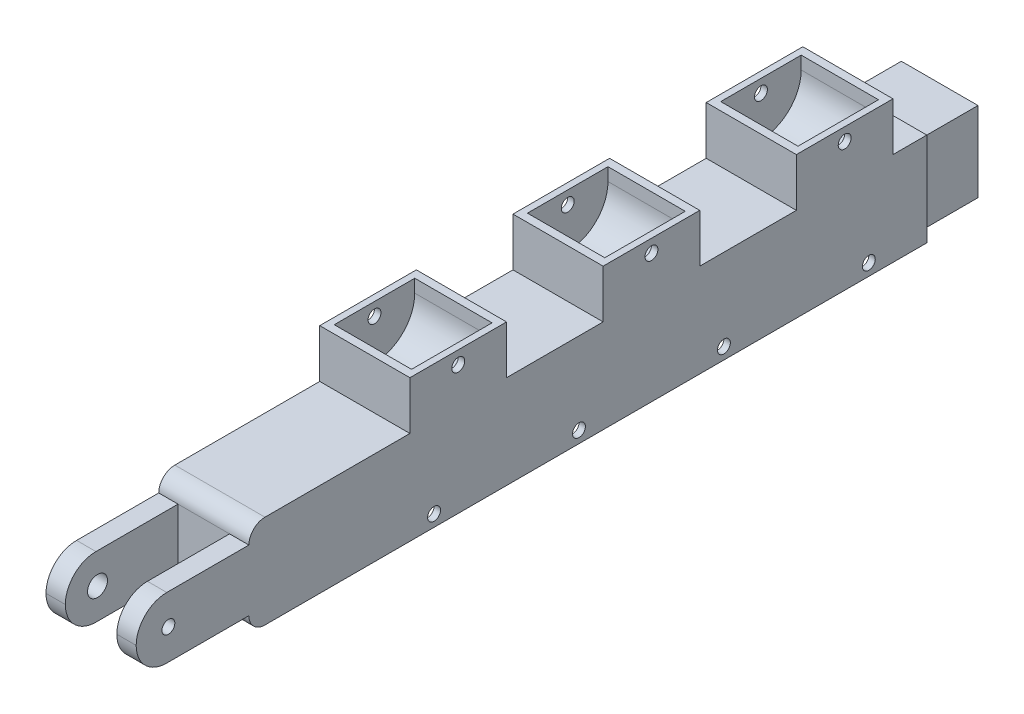
SolidWorks part; units mm, degrees
ref_plane "前视基准面" through (0, 0, 0) normal (0, 0, 1) x (1, 0, 0)
ref_plane "上视基准面" through (0, 0, 0) normal (0, 1, 0) x (1, 0, 0)
ref_plane "右视基准面" through (0, 0, 0) normal (1, 0, 0) x (0, 0, -1)
other "Configuration Table"
sketch "草图1" plane through (0, 0, 0) normal (1, 0, 0) x (0, 0, -1)
  line L0 (-150, 0) -> (150, 0) construction
  line L1 (-125, 14.5) -> (125, 14.5)
  line L2 (-125, 14.5) -> (-125, -14.5)
  line L3 (-125, -14.5) -> (125, -14.5)
  line L4 (125, 14.5) -> (125, -14.5)
  line L5 (-72.5, 29.5) -> (-72.5, 25.5)
  line L6 (-75, 14.5) -> (-45, 14.5)
  line L7 (-75, 14.5) -> (-75, 29.5)
  line L8 (-120, 10.8586) -> (120, 10.8586)
  line L9 (-120, 10.8586) -> (-120, -10.8586)
  line L10 (-120, -10.8586) -> (120, -10.8586)
  line L11 (120, 10.8586) -> (120, -10.8586)
  line L12 (-120, 10.8586) -> (120, -10.8586) construction
  line L13 (-120, -10.8586) -> (120, 10.8586) construction
  line L14 (-75, 29.5) -> (-45, 29.5)
  line L15 (-45, 14.5) -> (-45, 29.5)
  line L16 (-15, 14.5) -> (15, 14.5)
  line L17 (-15, 14.5) -> (-15, 29.5)
  line L18 (-15, 29.5) -> (15, 29.5)
  line L19 (15, 14.5) -> (15, 29.5)
  line L20 (45, 14.5) -> (75, 14.5)
  line L21 (45, 14.5) -> (45, 29.5)
  line L22 (45, 29.5) -> (75, 29.5)
  line L23 (75, 14.5) -> (75, 29.5)
  line L24 (-47.5, 29.5) -> (-47.5, 25.5)
  line L25 (-12.5, 29.5) -> (-12.5, 25.5)
  line L26 (12.5, 29.5) -> (12.5, 25.5)
  line L27 (47.5, 29.5) -> (47.5, 25.5)
  line L29 (72.5, 25.5) -> (72.5, 29.5)
  circle A2 centre (-67.5, -10.8586) radius 2
  circle A3 centre (-22.5, -10.8586) radius 2
  circle A4 centre (22.5, -10.8586) radius 2
  circle A5 centre (-60, 25.5) radius 2
  circle A6 centre (67.5, -10.8586) radius 2
  circle A7 centre (0, 25.5) radius 2
  circle A8 centre (60, 25.5) radius 2
  circle A9 centre (-60, 25.5) radius 12.5
  circle A10 centre (0, 25.5) radius 12.5
  circle A11 centre (60, 25.5) radius 12.5
  circle A12 centre (-67.5, -10.8586) radius 12.5
  circle A13 centre (-22.5, -10.8586) radius 12.5
  circle A14 centre (22.5, -10.8586) radius 12.5
  circle A15 centre (67.5, -10.8586) radius 12.5
  circle A16 centre (150, 0) radius 2
  circle A17 centre (-150, 0) radius 2
  circle A18 centre (-150, 0) radius 3.1
  point P10 (0, 0)
  point P12 (-125, 0)
  point P56 (-60, 29.5)
  point P62 (0, 29.5)
  point P64 (60, 29.5)
  dimension "D2" = 5
  dimension "D4" = 25
  dimension "D8" = 4
  dimension "D18" = 4
  dimension "D22" = 6.2
  dimension "D1" = 300
  dimension "D3" = 5
  dimension "D5" = 14.5
  dimension "D6" = 120
  dimension "D7" = 10.8586
  dimension "D9" = 52.5
  dimension "D10" = 45
  dimension "D11" = 45
  dimension "D12" = 45
  dimension "D13" = 60
  dimension "D14" = 60
  dimension "D15" = 60
  dimension "D16" = 60
  dimension "D17" = 52.5
  dimension "D19" = 30
  dimension "D20" = 4
  dimension "D21" = 15
extrude "凸台-拉伸1" add sketch "草图1" along normal blind 28 contours L1 L4 L3 L2 | L14 L15 L6 L7 | L18 L19 L16 L17 | L22 L23 L20 L21
extrude "切除-拉伸1" cut sketch "草图1<3>" along normal through all contours A2 | A3 | A4 | A6 | A8 | A7 | A5
sketch "草图1<3>" plane through (0, 0, 0) normal (1, 0, 0) x (0, 0, -1) same geometry as "草图1"
extrude "切除-拉伸2" cut sketch "草图1<5>" along normal offset from surface (24 mm away) 2 from offset 2 contours A9 L14 L5 | A9 L24 L14 | A10 L18 L25 | A10 L26 L18 | A11 L22 L27 | A11 L29 L22 | A12 | A9 | A13 | A10 | A14 | A11 | A15 region at (0, 28.5053, 72.3037) region at (0, 28.5053, 47.6963) region at (0, 28.5053, 12.3037) region at (0, 28.5053, -12.3037) region at (0, 28.5053, -47.6963) region at (0, 28.5053, -72.3037) up to face at (28, -10.8586, 65.5)
sketch "草图1<5>" plane through (0, 0, 0) normal (1, 0, 0) x (0, 0, -1) same geometry as "草图1"
sketch "草图3" plane through (0, 0, 125) normal (0, 0, 1) x (1, 0, 0)
  line L0 (28, 14.5) -> (28, -14.5) construction
  line L1 (28, 9.5) -> (22, 9.5)
  line L2 (28, 9.5) -> (28, -9.5)
  line L3 (28, -9.5) -> (22, -9.5)
  line L4 (22, 9.5) -> (22, -9.5)
  line L5 (28, 14.5) -> (0, 14.5) construction
  line L6 (28, -14.5) -> (0, -14.5) construction
  line L7 (0, 14.5) -> (0, -14.5) construction
  line L8 (0, 9.5) -> (6, 9.5)
  line L9 (0, 9.5) -> (0, -9.5)
  line L10 (0, -9.5) -> (6, -9.5)
  line L11 (6, 9.5) -> (6, -9.5)
  dimension "D1" = 6
  dimension "D2" = 5
  dimension "D3" = 5
extrude "凸台-拉伸2" add sketch "草图3" along normal blind 35 contours L1 L4 L3 L2
extrude "凸台-拉伸3" add sketch "草图3<3>" along normal blind 35 contours L2 L3 L4 L1 | L9 L10 L11 L8
sketch "草图3<3>" plane through (0, 0, 125) normal (0, 0, 1) x (1, 0, 0) same geometry as "草图3"
extrude "切除-拉伸3" cut sketch "草图1<6>" along normal through all contours A17
sketch "草图1<6>" plane through (0, 0, 0) normal (1, 0, 0) x (0, 0, -1) same geometry as "草图1"
extrude "切除-拉伸7" cut sketch "草图1<8>" along normal up to next contours A18
sketch "草图1<8>" plane through (0, 0, 0) normal (1, 0, 0) x (0, 0, -1) same geometry as "草图1"
fillet "圆角1" radius 9.5 4 edges at (25, 9.5, 160) (25, -9.5, 160) (3, -9.5, 160) (3, 9.5, 160)
fillet "圆角2" radius 5 2 edges at (14, -14.5, 125) (14, 14.5, 125)
sketch "草图4" plane through (0, 0, -125) normal (0, 0, -1) x (-1, 0, 0)
  line L1 (-28, 14.5) -> (0, 14.5) construction
  circle A0 centre (-14, 0) radius 5.1
  point P7 (-14, 14.5)
  dimension "D1" = 10.2
extrude "切除-拉伸4" cut sketch "草图4" against normal blind 31.5
extrude "切除-拉伸5" cut sketch "草图4<2>" against normal offset from surface (21.5 mm away) 10 flip side to cut up to face at (8.9, 0, -93.5)
sketch "草图4<2>" plane through (0, 0, -125) normal (0, 0, -1) x (-1, 0, 0) same geometry as "草图4"
sketch "草图5" plane through (0, 0, -103.5) normal (0, 0, -1) x (-1, 0, 0)
  line L0 (-28, 14.5) -> (0, 14.5) construction
  line L1 (-25.9, -12.4) -> (-2.1, -12.4)
  line L2 (-25.9, -12.4) -> (-25.9, 12.4)
  line L3 (-25.9, 12.4) -> (-2.1, 12.4)
  line L4 (-2.1, -12.4) -> (-2.1, 12.4)
  line L5 (-25.9, -12.4) -> (-2.1, 12.4) construction
  line L6 (-25.9, 12.4) -> (-2.1, -12.4) construction
  line L7 (0, -14.5) -> (0, 14.5) construction
  circle A0 centre (-14, 0) radius 5.1 construction
  point P0 (-14, 0)
  dimension "D1" = 2.1
  dimension "D2" = 2.1
extrude "切除-拉伸6" cut sketch "草图5" against normal blind 18 flip side to cut contours L3 L4 L1 L2
